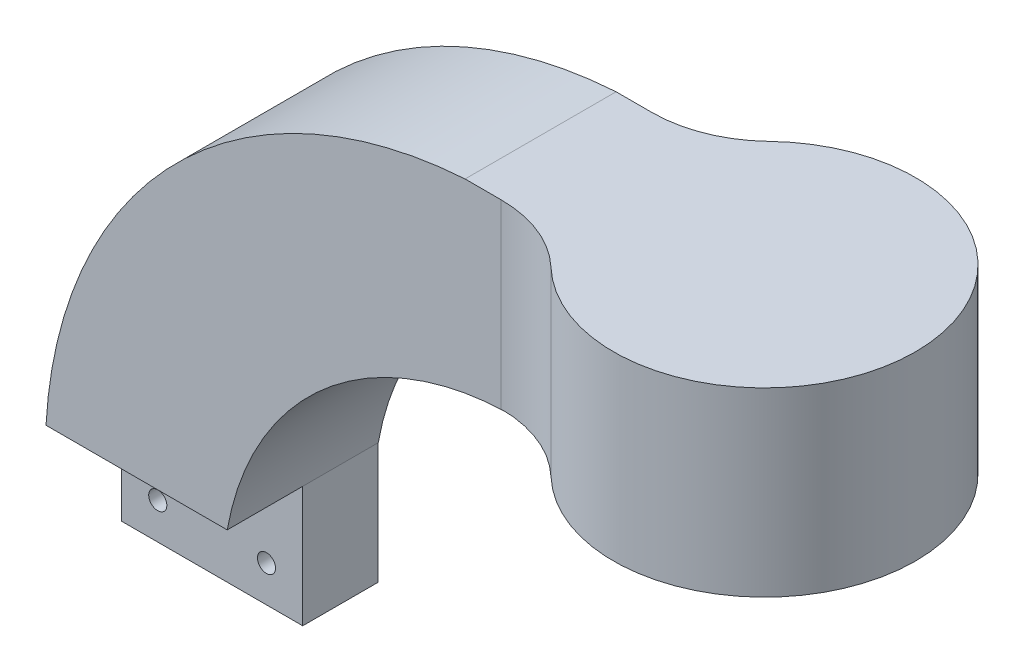
SolidWorks part; units mm, degrees
material "ABS"
ref_plane "Front Plane" through (0, 0, 0) normal (0, 0, 1) x (1, 0, 0)
ref_plane "Top Plane" through (0, 0, 0) normal (0, 1, 0) x (1, 0, 0)
ref_plane "Right Plane" through (0, 0, 0) normal (1, 0, 0) x (0, 0, -1)
sketch "Sketch1" plane through (0, 0, 0) normal (0, 0, 1) x (1, 0, 0)
  line L0 (69.3749, 90) -> (120, 90)
  line L1 (0, 0) -> (30, 0)
  line L2 (0, 0) -> (0, 20)
  line L3 (20, 90) -> (30, 90)
  line L4 (30, 0) -> (30, 20)
  line L5 (20, 90) -> (30, 90)
  line L7 (76.2846, 60) -> (120, 60)
  line L8 (120, 90) -> (120, 60)
  arc A1 (30, 20) -> (79.2135, 60) centre (77.7491, 11.5271) cw
  arc A2 (0, 20) -> (78.8823, 90) centre (74.1286, 15.9111) cw
  dimension "D4" = 20
  dimension "D5" = 20
  dimension "D1" = 30
  dimension "D2" = 30
  dimension "D3" = 90
extrude "Boss-Extrude1" add sketch "Sketch1" along normal blind 25 contours L2 L1 L4 L7 L8 L5 L3 region at (51.6447, 55.6367, 0)
sketch "Sketch3" plane through (0, 90, 0) normal (0, 1, 0) x (1, 0, 0)
  line L0 (120, -12.5) -> (92.8851, -12.5) construction
  line L1 (120, -25) -> (120, 0) construction
  line L2 (69.3749, 0) -> (69.3749, -25)
  line L3 (69.3749, -25) -> (75.3178, -25)
  line L4 (69.3749, -25) -> (120, -25) construction
  line L5 (69.3749, 0) -> (75.3178, 0)
  line L6 (69.3749, 0) -> (120, 0) construction
  arc A0 (89.151, -30.5556) -> (89.151, 5.5556) centre (106.4426, -12.5) ccw
  arc A1 (75.3178, -25) -> (89.151, -30.5556) centre (75.3178, -45) cw
  arc A2 (75.3178, 0) -> (89.151, 5.5556) centre (75.3178, 20) ccw
  point P17 (84.7919, -25)
  point P20 (84.7919, 0)
  dimension "D1" = 50
  dimension "D2" = 20
extrude "Boss-Extrude3" add sketch "Sketch3" against normal up to surface (30 mm away) up to face at (99.6068, 60, 12.5)
ref_axis "Axis1" through (106.4426, 60, 12.5) along (0, 1, 0)
sketch "Sketch4" plane through (0, 0, 0) normal (1, 0, 0) x (0, 0, -1)
  line L0 (-25, 0) -> (0, 0) construction
  line L1 (-12.5, 0) -> (-42.5, 0)
  line L2 (-12.5, 0) -> (-12.5, 20)
  line L3 (-12.5, 20) -> (-42.5, 20)
  line L4 (-42.5, 0) -> (-42.5, 20)
  dimension "D1" = 30
  dimension "D2" = 20
extrude "Cut-Extrude1" cut sketch "Sketch4" along normal blind 49
sketch "Sketch5" plane through (0, 0, 12.5) normal (0, 0, 1) x (1, 0, 0)
  line L0 (30, 14) -> (0, 14) construction
  line L1 (30, 20) -> (30, 0) construction
  line L2 (0, 20) -> (0, 0) construction
  line L3 (30, 20) -> (0, 20) construction
  line L4 (30, 6) -> (0, 6) construction
  line L6 (30, 0) -> (0, 0) construction
  line L7 (0, 0) -> (0, 20) construction
  line L8 (30, 0) -> (30, 20) construction
  circle A0 centre (24, 6) radius 1.5
  circle A1 centre (6, 6) radius 1.5
  circle A2 centre (15, 14) radius 1.5
  dimension "D2" = 3
  dimension "D3" = 3
  dimension "D4" = 3
  dimension "D1" = 6
  dimension "D5" = 15
  dimension "D6" = 6
  dimension "D7" = 6
  dimension "D8" = 6
extrude "Cut-Extrude2" cut sketch "Sketch5" against normal blind 49
